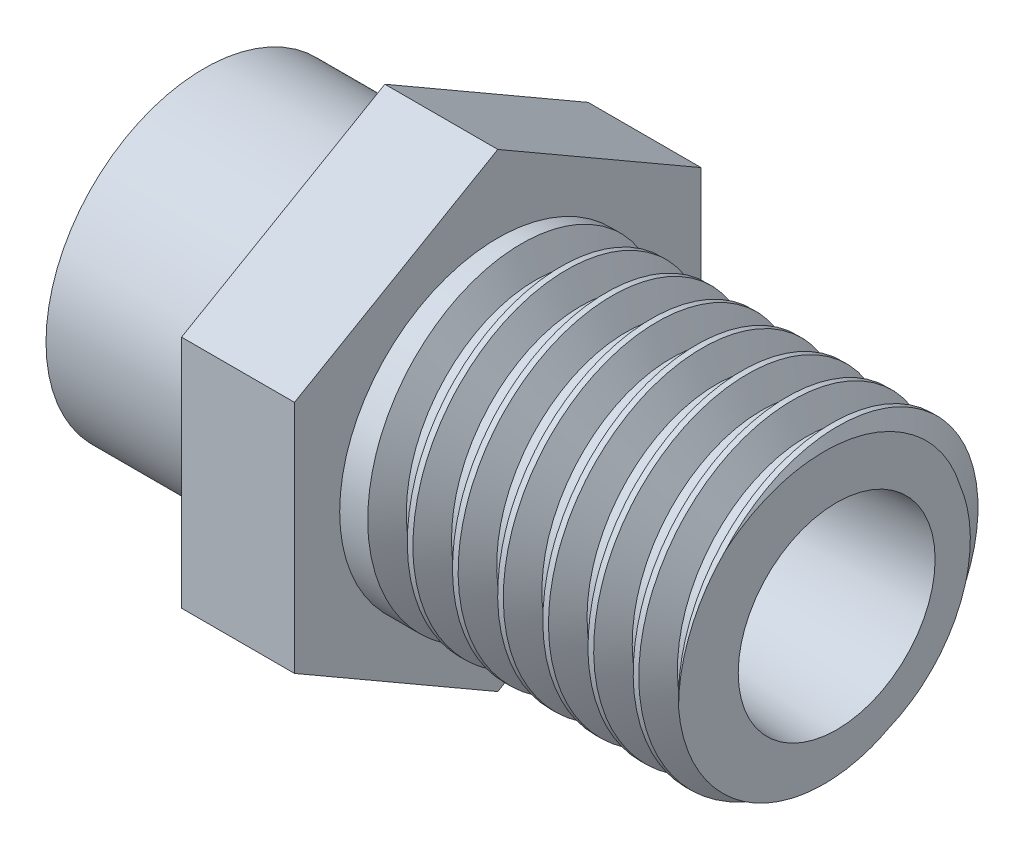
SolidWorks part; units mm, degrees
material "6061-T6 (SS)"
ref_plane "Alzado" through (0, 0, 0) normal (0, 0, 1) x (1, 0, 0)
ref_plane "Planta" through (0, 0, 0) normal (0, 1, 0) x (1, 0, 0)
ref_plane "Vista lateral" through (0, 0, 0) normal (1, 0, 0) x (0, 0, -1)
ref_plane "Plano2" through (-32, 0, 0) normal (1, 0, 0) x (0, 0, -1)
sketch "Sk_barril" plane through (-32, 0, 0) normal (1, 0, 0) x (0, 0, -1)
  circle A0 centre (-60.4, -16) radius 3.5
  circle A1 centre (-60.4, -16) radius 1.2
extrude "Barril" add sketch "Sk_barril" against normal blind 14 from offset 2
ref_plane "Plano4" through (-40, 0, 0) normal (1, 0, 0) x (0, 0, -1)
sketch "Sk_contratuerca" plane through (-40, 0, 0) normal (1, 0, 0) x (0, 0, -1)
  line L0 (-60.4, -10.8038) -> (-64.9, -13.4019)
  line L1 (-64.9, -13.4019) -> (-64.9, -18.5981)
  line L2 (-64.9, -18.5981) -> (-60.4, -21.1962)
  line L3 (-60.4, -21.1962) -> (-55.9, -18.5981)
  line L4 (-55.9, -18.5981) -> (-55.9, -13.4019)
  line L5 (-55.9, -13.4019) -> (-60.4, -10.8038)
  circle A0 centre (-60.4, -16) radius 1.2
extrude "Contratuerca" add sketch "Sk_contratuerca" along normal blind 2.5
sketch "Croquis1" plane through (-44, 0, 0) normal (-1, 0, 0) x (0, 0, 1)
  circle A0 centre (60.4, -16) radius 1.2
extrude "Cortar-Extruir1" cut sketch "Croquis1" against normal through all draft 4 draft outward yes
thread "Rosca1" pitch 1 method cut profile "Perfil de rosca1" start angle 0, offset 1, length 7.5, pitch 1, diameter 7
ref_plane "Plano5" through (-29, -16, 63.9) normal (0, -1, 0) x (0, 0, 1)
sketch "Perfil de rosca1" plane through (-29, -16, 63.9) normal (0, -1, 0) x (0, 0, 1)
  line L0 (0, 0) -> (0, 1) construction
  line L11 (0, 0) -> (0, 0.875)
  line L12 (0, 0.875) -> (-0.5413, 0.5625)
  line L13 (-0.5413, 0.5625) -> (-0.5413, 0.3125)
  line L15 (-0.5413, 0.3125) -> (0, 0)
  line L17 (-0.5413, 0.4375) -> (0, 0.4375) construction
  point P2 (0, 0)
  dimension "Pitch" = 1
  dimension "Profile_Angle" = 60
  dimension "Profile_Land" = 0.25
  dimension "Profile_Height" = 0.5413
